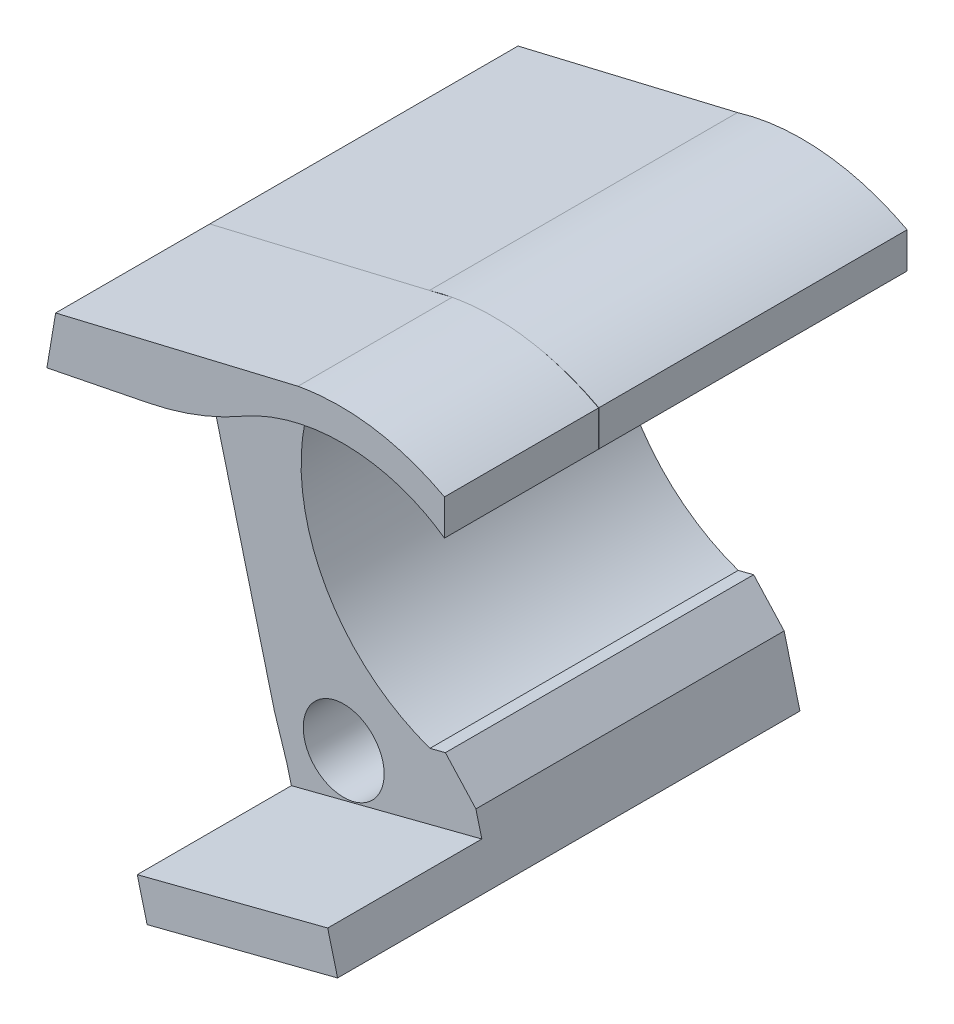
SolidWorks part; units mm, degrees
ref_plane "Plan de face" through (0, 0, 0) normal (0, 0, 1) x (1, 0, 0)
ref_plane "Plan de dessus" through (0, 0, 0) normal (0, 1, 0) x (1, 0, 0)
ref_plane "Plan de droite" through (0, 0, 0) normal (1, 0, 0) x (0, 0, -1)
sketch "Esquisse1" plane through (0, 0, 0) normal (0, 0, 1) x (1, 0, 0)
  line L0 (-12.8784, 6.5154) -> (-8.0203, -12.3632)
  line L2 (2.0789, -9.432) -> (3.0789, -9.1746)
  line L8 (13.0361, 12.8665) -> (13.0361, 15.185)
  line L10 (5.0579, -11.3462) -> (6.0841, -15.3342)
  line L11 (6.0841, -15.3342) -> (-6.2737, -18.5142)
  line L12 (-6.2737, -18.5142) -> (-7.1843, -14.9757)
  line L13 (-12.964, 8.4074) -> (-12.2096, 12.8879)
  line L14 (-12.2096, 12.8879) -> (2.0306, 16.269)
  line L15 (3.0789, -9.1746) -> (5.0579, -11.3462)
  line L16 (-7.1843, -14.9757) -> (-8.0203, -12.3632)
  circle A0 centre (-8.5264, 7.6602) radius 2.625
  circle A1 centre (-3.5203, -12.3632) radius 2.625
  arc A3 (-12.964, 8.4074) -> (-12.8784, 6.5154) centre (-8.5264, 7.6602) ccw
  arc A5 (-0.3329, 13.0097) -> (2.0789, -9.432) centre (6.2171, 2.3632) ccw
  arc A6 (13.0361, 15.185) -> (2.0306, 16.269) centre (6.2171, 2.3632) ccw
  spline S0 degree 3 poles (-0.3329, 13.0097) (3.6353, 15.4301) (9.0612, 15.6828) (13.0361, 12.8665) knots 0.137989 0.137989 0.137989 0.137989 1 1 1 1
extrude "Boss.-Extru.1" add sketch "Esquisse1" along normal blind 20
sketch "Esquisse2" plane through (0, 0, 20) normal (0, 0, 1) x (1, 0, 0)
  line L0 (3.5157, 16.6321) -> (-12.2096, 12.8879)
  line L1 (-12.2096, 12.8879) -> (-12.7766, 9.5203)
  line L2 (-12.7766, 9.5203) -> (-2.1488, 11.651)
  line L3 (13.0203, 12.8496) -> (13.0203, 15.1681)
  line L10 (-12.2096, 12.8879) -> (-12.964, 8.4074) construction
  line L11 (-6.2737, -18.5142) -> (-6.9143, -16.0251)
  line L12 (-7.1843, -14.9757) -> (-6.2737, -18.5142) construction
  line L13 (-6.9143, -16.0251) -> (5.4436, -12.845)
  line L14 (6.0841, -15.3342) -> (5.0579, -11.3462) construction
  line L15 (5.4436, -12.845) -> (6.0841, -15.3342)
  line L16 (6.0841, -15.3342) -> (-6.2737, -18.5142)
  arc A0 (13.0361, 15.185) -> (2.0306, 16.269) centre (6.2171, 2.3632) ccw construction
  arc A1 (-0.3329, 13.0097) -> (2.0789, -9.432) centre (6.2171, 2.3632) ccw construction
  arc A3 (13.0361, 15.185) -> (2.0306, 16.269) centre (6.2171, 2.3632) ccw construction
  spline S0 degree 3 poles (-2.1488, 11.651) (1.8255, 15.2508) (8.4015, 16.1219) (13.0203, 12.8496) knots 0 0 0 0 1 1 1 1
  spline S1 degree 2 poles (13.0203, 15.1681) (8.5435, 17.5408) (3.5157, 16.6321) knots 0 0 0 1 1 1
extrude "Boss.-Extru.2" add sketch "Esquisse2" along normal blind 10
fillet "Congé1" radius 20 1 edges
